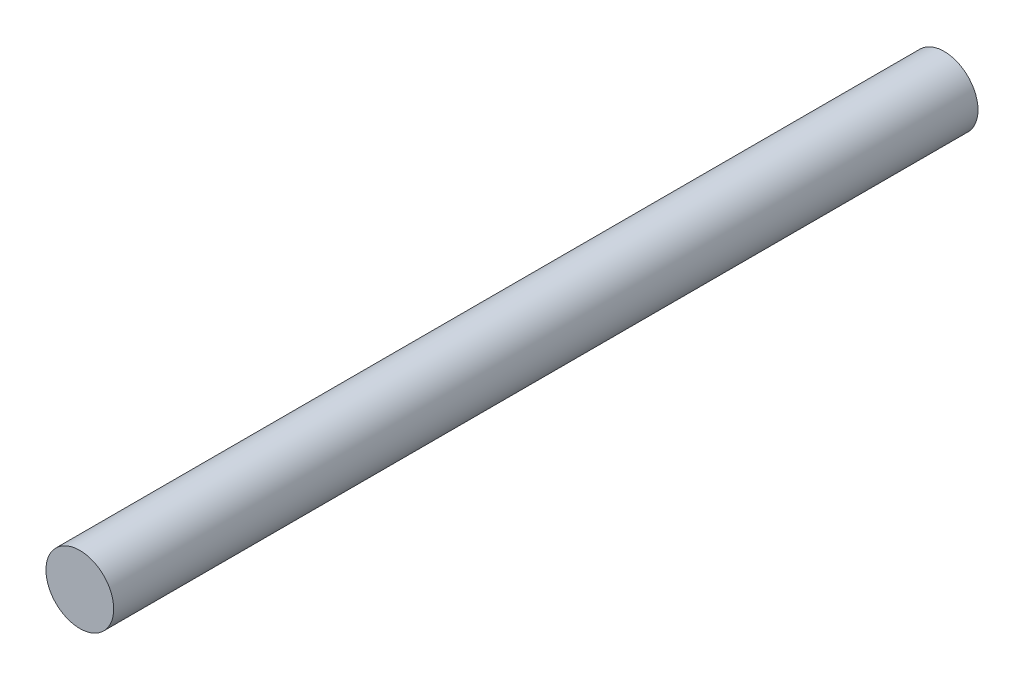
SolidWorks part; units mm, degrees
ref_plane "Alzado" through (0, 0, 0) normal (0, 0, 1) x (1, 0, 0)
ref_plane "Planta" through (0, 0, 0) normal (0, 1, 0) x (1, 0, 0)
ref_plane "Vista lateral" through (0, 0, 0) normal (1, 0, 0) x (0, 0, -1)
sketch "Croquis1" plane through (0, 0, 0) normal (0, 0, 1) x (1, 0, 0)
  circle A0 centre (0, 0) radius 3.175
  dimension "D1" = 6.35
extrude "Saliente-Extruir1" add sketch "Croquis1" along normal mid plane 81
